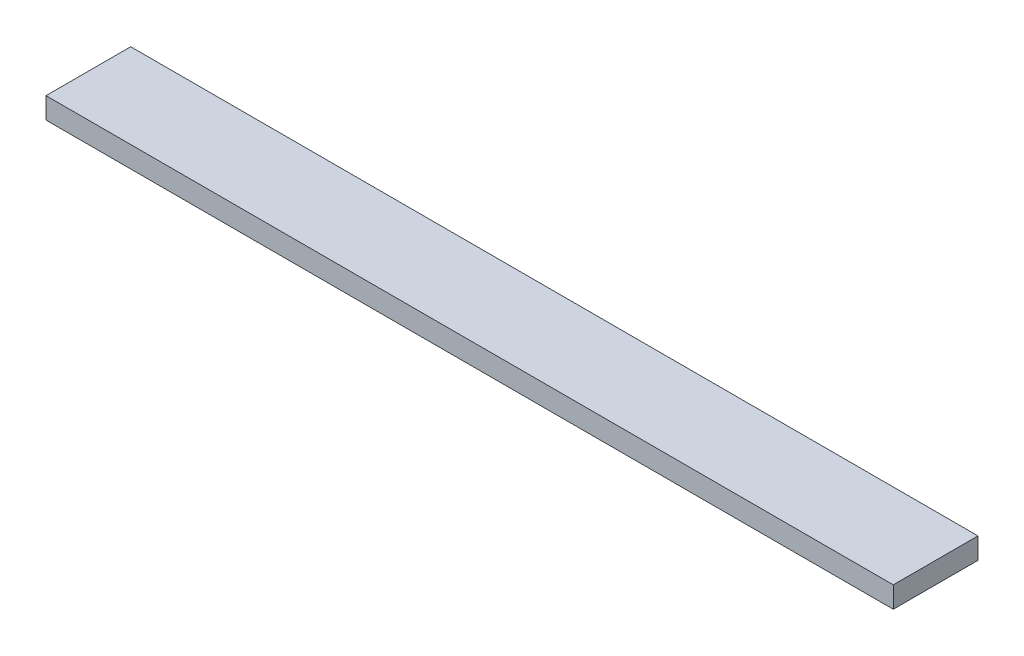
SolidWorks part; units mm, degrees
ref_plane "Plan de face" through (0, 0, 0) normal (0, 0, 1) x (1, 0, 0)
ref_plane "Plan de dessus" through (0, 0, 0) normal (0, 1, 0) x (1, 0, 0)
ref_plane "Plan de droite" through (0, 0, 0) normal (1, 0, 0) x (0, 0, -1)
sketch "Esquisse1" plane through (0, 0, 0) normal (1, 0, 0) x (0, 0, -1)
  line L0 (-4, 0) -> (4, 0)
  line L1 (4, 0) -> (4, -2)
  line L2 (4, -2) -> (2.5, -3.5)
  line L3 (2.5, -3.5) -> (-2.5, -3.5)
  line L4 (-2.5, -3.5) -> (-4, -2)
  line L5 (-4, -2) -> (-4, 0)
  line L6 (-4, -2) -> (4, -2) construction
  line L7 (0, 0) -> (0, -3.5) construction
  dimension "D1" = 2
  dimension "D2" = 8
  dimension "D3" = 1.5
extrude "Boss.-Extru.1" add sketch "Esquisse1" along normal blind 40 and the other way blind 40
chamfer "Chanfrein1" distance 1.5 angle 45 2 edges at (40, -3.5, 0) (-40, -3.5, 0)
